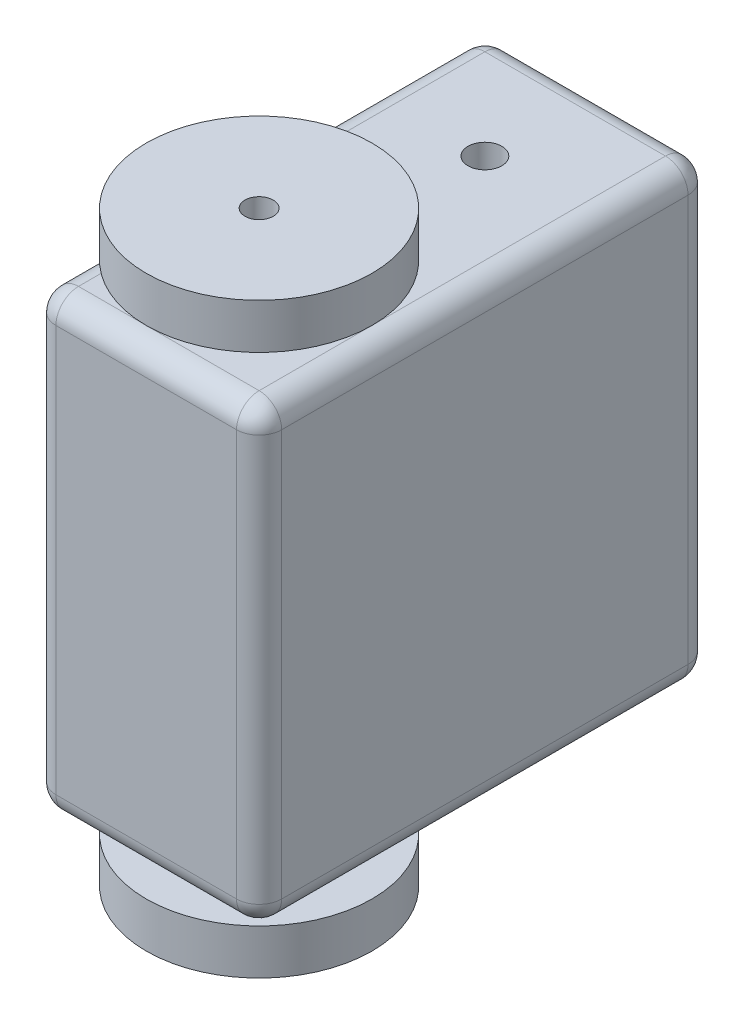
SolidWorks part; units mm, degrees
ref_plane "Front" through (0, 0, 0) normal (0, 0, 1) x (1, 0, 0)
ref_plane "Top" through (0, 0, 0) normal (0, 1, 0) x (1, 0, 0)
ref_plane "Right" through (0, 0, 0) normal (1, 0, 0) x (0, 0, -1)
sketch "草图1" plane through (0, 0, 0) normal (1, 0, 0) x (0, 0, -1)
  line L1 (20, -20) -> (-20, -20)
  line L2 (20, -20) -> (20, 20)
  line L3 (20, 20) -> (-20, 20)
  line L4 (-20, -20) -> (-20, 20)
  line L5 (20, -20) -> (-20, 20) construction
  line L6 (20, 20) -> (-20, -20) construction
  point P0 (0, 0)
  dimension "D1" = 40
  dimension "D2" = 40
extrude "凸台-拉伸1" add sketch "草图1" along normal mid plane 20
sketch "草图2" plane through (0, 20, 0) normal (0, 1, 0) x (1, 0, 0)
  line L0 (0, -20) -> (0, 20) construction
  line L1 (10, -20) -> (-10, -20) construction
  line L2 (10, 20) -> (-10, 20) construction
  circle A0 centre (0, -10) radius 5
  dimension "D1" = 10
  dimension "D2" = 10
extrude "凸台-拉伸2" add sketch "草图2" along normal blind 1
sketch "草图3" plane through (0, 21, 0) normal (0, 1, 0) x (1, 0, 0)
  circle A0 centre (0, -10) radius 2.5
  circle A1 centre (0, -10) radius 5 construction
  dimension "D1" = 5
extrude "凸台-拉伸3" add sketch "草图3" along normal blind 1
sketch "草图4" plane through (0, 22, 0) normal (0, 1, 0) x (1, 0, 0)
  circle A0 centre (0, -10) radius 10
  circle A1 centre (0, -10) radius 2.5 construction
  dimension "D1" = 20
extrude "凸台-拉伸4" add sketch "草图4" along normal blind 4
sketch "草图5" plane through (0, 26, 0) normal (0, 1, 0) x (1, 0, 0)
  circle A0 centre (0, -10) radius 1.25
  circle A1 centre (0, -10) radius 10 construction
  dimension "D1" = 2.5
extrude "切除-拉伸1" cut sketch "草图5" against normal up to surface (46 mm away)
mirror "镜向1" about plane through (0, 0, 0) normal (0, 1, 0) of "切除-拉伸1", "凸台-拉伸4", "凸台-拉伸3", "凸台-拉伸2"
fillet "圆角1" radius 2 13 edges at (0, 20, 20) (0, 20, 5) (0, -20, 20) (0, -20, -20) (0, 20, -20) (-10, -20, 0) (-10, 20, 0) (-10, 0, 20) (-10, 0, -20) (10, 0, -20) (10, -20, 0) (10, 0, 20) (10, 20, 0)
sketch "草图6" plane through (0, 20, 0) normal (0, 1, 0) x (1, 0, 0)
  line L0 (-8, 20) -> (8, 20) construction
  circle A0 centre (0, 10) radius 1.5
  dimension "D1" = 10
  dimension "D2" = 3
extrude "切除-拉伸2" cut sketch "草图6" against normal blind 3
mirror "镜向2" about plane through (0, 0, 0) normal (0, 1, 0) of "切除-拉伸2"
